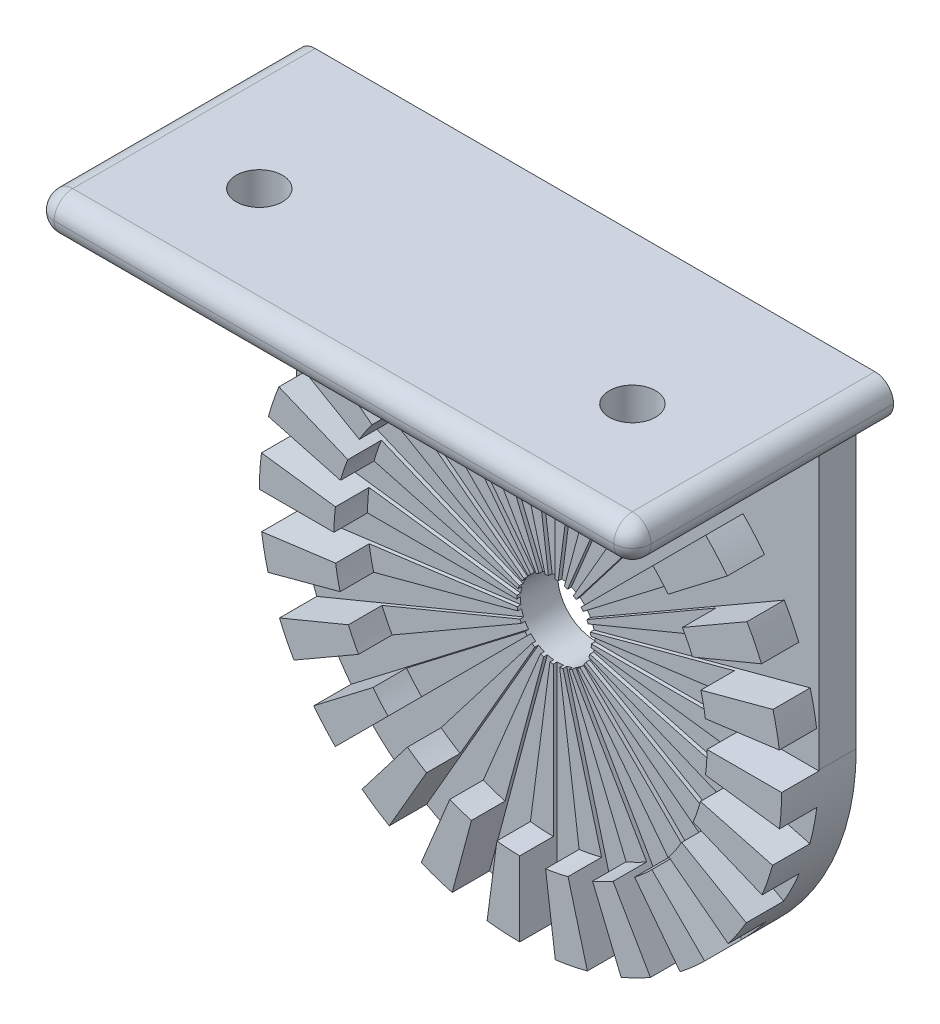
SolidWorks part; units mm, degrees
note: The reader was unsure of these and kept them because the rebuilt part matched: shared geometry of "Sketch1<5>".
ref_plane "Front Plane" through (0, 0, 0) normal (0, 0, 1) x (1, 0, 0)
ref_plane "Top Plane" through (0, 0, 0) normal (0, 1, 0) x (1, 0, 0)
ref_plane "Right Plane" through (0, 0, 0) normal (1, 0, 0) x (0, 0, -1)
sketch "Sketch1" plane through (0, 0, 0) normal (0, 0, 1) x (1, 0, 0)
  line L0 (0, 0) -> (0, 35) construction
  line L1 (0, 0) -> (-35, 0) construction
  line L2 (0, 0) -> (-34.7006, 4.5684) construction
  line L3 (0, 0) -> (-33.8074, 9.0587) construction
  line L4 (0, 0) -> (-32.3358, 13.3939) construction
  line L5 (0, 0) -> (-30.3109, 17.5) construction
  line L6 (0, 0) -> (-27.7674, 21.3067) construction
  line L7 (0, 0) -> (-24.7487, 24.7487) construction
  line L8 (0, 0) -> (-21.3067, 27.7674) construction
  line L9 (0, 0) -> (-17.5, 30.3109) construction
  line L10 (0, 0) -> (-13.3939, 32.3358) construction
  line L11 (0, 0) -> (-9.0587, 33.8074) construction
  line L12 (0, 0) -> (-4.5684, 34.7006) construction
  line L13 (0, 0) -> (0, 35) construction
  line L14 (0, 0) -> (4.5684, 34.7006) construction
  line L15 (0, 0) -> (9.0587, 33.8074) construction
  line L16 (0, 0) -> (13.3939, 32.3358) construction
  line L17 (0, 0) -> (17.5, 30.3109) construction
  line L18 (0, 0) -> (21.3067, 27.7674) construction
  line L19 (0, 0) -> (24.7487, 24.7487) construction
  line L20 (0, 0) -> (27.7674, 21.3067) construction
  line L21 (0, 0) -> (30.3109, 17.5) construction
  line L22 (0, 0) -> (32.3358, 13.3939) construction
  line L23 (0, 0) -> (33.8074, 9.0587) construction
  line L24 (0, 0) -> (34.7006, 4.5684) construction
  line L25 (0, 0) -> (35, 0) construction
  line L26 (0, 0) -> (34.7006, -4.5684) construction
  line L27 (0, 0) -> (33.8074, -9.0587) construction
  line L28 (0, 0) -> (32.3358, -13.3939) construction
  line L29 (0, 0) -> (30.3109, -17.5) construction
  line L30 (0, 0) -> (27.7674, -21.3067) construction
  line L31 (0, 0) -> (24.7487, -24.7487) construction
  line L32 (0, 0) -> (21.3067, -27.7674) construction
  line L33 (0, 0) -> (17.5, -30.3109) construction
  line L34 (0, 0) -> (13.3939, -32.3358) construction
  line L35 (0, 0) -> (9.0587, -33.8074) construction
  line L36 (0, 0) -> (4.5684, -34.7006) construction
  line L37 (0, 0) -> (0, -35) construction
  line L38 (0, 0) -> (-4.5684, -34.7006) construction
  line L39 (0, 0) -> (-9.0587, -33.8074) construction
  line L40 (0, 0) -> (-13.3939, -32.3358) construction
  line L41 (0, 0) -> (-17.5, -30.3109) construction
  line L42 (0, 0) -> (-21.3067, -27.7674) construction
  line L43 (0, 0) -> (-24.7487, -24.7487) construction
  line L44 (0, 0) -> (-27.7674, -21.3067) construction
  line L45 (0, 0) -> (-30.3109, -17.5) construction
  line L46 (0, 0) -> (-32.3358, -13.3939) construction
  line L47 (0, 0) -> (-33.8074, -9.0587) construction
  line L48 (0, 0) -> (-34.7006, -4.5684) construction
  line L49 (0, 0) -> (0, -242.3631) construction
  line L50 (0, 0) -> (261.9224, -229.7808) construction
  line L51 (0, 0) -> (-86.1053, -174.4963) construction
  line L52 (0, 0) -> (-59.0107, -296.2868) construction
  line L53 (0, 0) -> (171.8721, -257.7552) construction
  line L54 (-1.5257, 0.1) -> (-35, 0.1)
  line L55 (-1.5257, 0.1) -> (-34.7136, 4.4693)
  line L56 (-1.4478, 0.4915) -> (-33.7815, 9.1553)
  line L57 (-1.4478, 0.4915) -> (-32.3741, 13.3015)
  line L58 (-1.2713, 0.8495) -> (-30.2609, 17.5866)
  line L59 (-1.2713, 0.8495) -> (-27.8282, 21.2273)
  line L60 (-1.0081, 1.1495) -> (-24.678, 24.8194)
  line L61 (-1.0081, 1.1495) -> (-21.386, 27.7065)
  line L62 (-0.6763, 1.3713) -> (-17.4134, 30.3609)
  line L63 (-0.6763, 1.3713) -> (-13.4863, 32.2975)
  line L64 (-0.2983, 1.4996) -> (-8.9621, 33.8333)
  line L65 (-0.2983, 1.4996) -> (-4.6676, 34.6875)
  line L66 (0.1, 1.5257) -> (0.1, 35)
  line L67 (0.1, 1.5257) -> (4.4693, 34.7136)
  line L68 (0.4915, 1.4478) -> (9.1553, 33.7815)
  line L69 (0.4915, 1.4478) -> (13.3015, 32.3741)
  line L70 (0.8495, 1.2713) -> (17.5866, 30.2609)
  line L71 (0.8495, 1.2713) -> (21.2273, 27.8282)
  line L72 (1.1495, 1.0081) -> (24.8194, 24.678)
  line L73 (1.1495, 1.0081) -> (27.7065, 21.386)
  line L74 (1.3713, 0.6763) -> (30.3609, 17.4134)
  line L75 (1.3713, 0.6763) -> (32.2975, 13.4863)
  line L76 (1.4996, 0.2983) -> (33.8333, 8.9621)
  line L77 (1.4996, 0.2983) -> (34.6875, 4.6676)
  line L78 (1.5257, -0.1) -> (35, -0.1)
  line L79 (1.5257, -0.1) -> (34.7136, -4.4693)
  line L80 (1.4478, -0.4915) -> (33.7815, -9.1553)
  line L81 (1.4478, -0.4915) -> (32.3741, -13.3015)
  line L82 (1.2713, -0.8495) -> (30.2609, -17.5866)
  line L83 (1.2713, -0.8495) -> (27.8282, -21.2273)
  line L84 (1.0081, -1.1495) -> (24.678, -24.8194)
  line L85 (1.0081, -1.1495) -> (21.386, -27.7065)
  line L86 (0.6763, -1.3713) -> (17.4134, -30.3609)
  line L87 (0.6763, -1.3713) -> (13.4863, -32.2975)
  line L88 (0.2983, -1.4996) -> (8.9621, -33.8333)
  line L89 (0.2983, -1.4996) -> (4.6676, -34.6875)
  line L90 (-0.1, -1.5257) -> (-0.1, -35)
  line L91 (-0.1, -1.5257) -> (-4.4693, -34.7136)
  line L92 (-0.4915, -1.4478) -> (-9.1553, -33.7815)
  line L93 (-0.4915, -1.4478) -> (-13.3015, -32.3741)
  line L94 (-0.8495, -1.2713) -> (-17.5866, -30.2609)
  line L95 (-0.8495, -1.2713) -> (-21.2273, -27.8282)
  line L96 (-1.1495, -1.0081) -> (-24.8194, -24.678)
  line L97 (-1.1495, -1.0081) -> (-27.7065, -21.386)
  line L98 (-1.3713, -0.6763) -> (-30.3609, -17.4134)
  line L99 (-1.3713, -0.6763) -> (-32.2975, -13.4863)
  line L100 (-1.4996, -0.2983) -> (-33.8333, -8.9621)
  line L101 (-1.4996, -0.2983) -> (-34.6875, -4.6676)
  line L102 (0, 0) -> (-192.6466, -219.5626) construction
  line L103 (0, 0) -> (183.0194, 0) construction
  circle A0 centre (0, 0) radius 35
  arc A1 (-34.7136, 4.4693) -> (-35, 0.1) centre (-1.5257, 0.1) ccw
  arc A2 (-32.3741, 13.3015) -> (-33.7815, 9.1553) centre (-1.4478, 0.4915) ccw
  arc A3 (-27.8282, 21.2273) -> (-30.2609, 17.5866) centre (-1.2713, 0.8495) ccw
  arc A4 (-21.386, 27.7065) -> (-24.678, 24.8194) centre (-1.0081, 1.1495) ccw
  arc A5 (-13.4863, 32.2975) -> (-17.4134, 30.3609) centre (-0.6763, 1.3713) ccw
  arc A6 (-4.6676, 34.6875) -> (-8.9621, 33.8333) centre (-0.2983, 1.4996) ccw
  arc A7 (4.4693, 34.7136) -> (0.1, 35) centre (0.1, 1.5257) ccw
  arc A8 (13.3015, 32.3741) -> (9.1553, 33.7815) centre (0.4915, 1.4478) ccw
  arc A9 (21.2273, 27.8282) -> (17.5866, 30.2609) centre (0.8495, 1.2713) ccw
  arc A10 (27.7065, 21.386) -> (24.8194, 24.678) centre (1.1495, 1.0081) ccw
  arc A11 (32.2975, 13.4863) -> (30.3609, 17.4134) centre (1.3713, 0.6763) ccw
  arc A12 (34.6875, 4.6676) -> (33.8333, 8.9621) centre (1.4996, 0.2983) ccw
  arc A13 (34.7136, -4.4693) -> (35, -0.1) centre (1.5257, -0.1) ccw
  arc A14 (32.3741, -13.3015) -> (33.7815, -9.1553) centre (1.4478, -0.4915) ccw
  arc A15 (27.8282, -21.2273) -> (30.2609, -17.5866) centre (1.2713, -0.8495) ccw
  arc A16 (21.386, -27.7065) -> (24.678, -24.8194) centre (1.0081, -1.1495) ccw
  arc A17 (13.4863, -32.2975) -> (17.4134, -30.3609) centre (0.6763, -1.3713) ccw
  arc A18 (4.6676, -34.6875) -> (8.9621, -33.8333) centre (0.2983, -1.4996) ccw
  arc A19 (-4.4693, -34.7136) -> (-0.1, -35) centre (-0.1, -1.5257) ccw
  arc A20 (-13.3015, -32.3741) -> (-9.1553, -33.7815) centre (-0.4915, -1.4478) ccw
  arc A21 (-21.2273, -27.8282) -> (-17.5866, -30.2609) centre (-0.8495, -1.2713) ccw
  arc A22 (-27.7065, -21.386) -> (-24.8194, -24.678) centre (-1.1495, -1.0081) ccw
  arc A23 (-32.2975, -13.4863) -> (-30.3609, -17.4134) centre (-1.3713, -0.6763) ccw
  arc A24 (-34.6875, -4.6676) -> (-33.8333, -8.9621) centre (-1.4996, -0.2983) ccw
  point P25 (0, 0)
  point P31 (0, 0)
  point P57 (0, 0)
  point P58 (0, 0)
  point P159 (0, 0)
  dimension "D1" = 70
  dimension "D8" = 24
  dimension "D2" = 11.264
  dimension "D3" = 48.74
  dimension "D4" = 26.264
  dimension "D5" = 33.696
  dimension "D9" = 41.264
  dimension "D7" = 0.1
  dimension "D6" = 48
extrude "Boss-Extrude2" add sketch "Sketch1" along normal blind 10 contours L55 A0 L54 | L57 A0 L56 | L59 A0 L58 | L61 A0 L60 | L63 A0 L62 | L65 A0 L64 | L67 A0 L66 | L69 A0 L68 | L71 A0 L70 | L73 A0 L72 | L75 A0 L74 | L77 A0 L76 | L79 A0 L78 | L81 A0 L80 | L83 A0 L82 | L85 A0 L84 | L87 A0 L86 | L89 A0 L88 | L91 A0 L90 | L93 A0 L92 | L95 A0 L94 | L97 A0 L96 | L101 A0 L100 | L99 A0 L98
extrude "Boss-Extrude3" add sketch "Sketch1<5>" along normal blind 5 contours L3 A0 L2 | L5 A0 L4 | L7 A0 L6 | L9 A0 L8 | L11 A0 L10 | L13 A0 L12 | L15 A0 L14 | L17 A0 L16 | L19 A0 L18 | L21 A0 L20 | L23 A0 L22 | L25 A0 L24 | L27 A0 L26 | L29 A0 L28 | L31 A0 L30 | L33 A0 L32 | L35 A0 L34 | L37 A0 L36 | L39 A0 L38 | L41 A0 L40 | L43 A0 L42 | L45 A0 L44 | L47 A0 L46 | L1 A0 L48
sketch "Sketch1<5>" plane through (0, 0, 0) normal (0, 0, 1) x (1, 0, 0) same geometry as "Sketch1"
sketch "Sketch3" plane through (0, 0, 0) normal (0, 0, 1) x (1, 0, 0)
  circle A0 centre (0, 0) radius 5
  dimension "D1" = 10
extrude "Cut-Extrude1" cut sketch "Sketch3" against normal through all and the other way through all
sketch "Sketch9" plane through (0, 0, 0) normal (0, 0, 1) x (1, 0, 0)
  circle A0 centre (0, 0) radius 25
  dimension "D1" = 50
extrude "Cut-Extrude6" cut sketch "Sketch9" along normal blind 5.5 from offset 5.5
ref_plane "Plane1" through (0, 40, 0) normal (0, 1, 0) x (1, 0, 0)
sketch "Sketch4" plane through (0, 40, 0) normal (0, 1, 0) x (1, 0, 0)
  line L0 (-68.9774, 0) -> (62.7068, 0) construction
  line L1 (40, -35) -> (-40, -35)
  line L2 (40, -35) -> (40, 0)
  line L4 (-40, -35) -> (-40, 0)
  line L5 (40, -35) -> (-40, 35) construction
  line L6 (40, 35) -> (-40, -35) construction
  line L7 (-40, 0) -> (40, 0)
  point P0 (0, 0)
  dimension "D1" = 80
  dimension "D2" = 35
  dimension "D3" = 40
extrude "Boss-Extrude4" add sketch "Sketch4" along normal blind 5 contours L2 L7 L4 L1
sketch "Sketch6" plane through (0, 45, 0) normal (0, 1, 0) x (1, 0, 0)
  line L0 (-40, -35) -> (-40, 0) construction
  line L2 (0, 0) -> (19.5699, 0) construction
  line L3 (0, 0) -> (0, 22.0266) construction
  line L4 (40, -35) -> (-40, -35) construction
  circle A1 centre (-25, -20) radius 3.1
  circle A2 centre (25, -20) radius 3.1
  dimension "D3" = 6.2
  dimension "D1" = 15
  dimension "D2" = 15
extrude "Cut-Extrude2" cut sketch "Sketch6" against normal through all
sketch "Sketch10" plane through (0, 0, 0) normal (0, 0, 1) x (1, 0, 0)
  line L0 (-35, 0) -> (-35, 40)
  line L2 (38.5, 40) -> (-38.5, 40) construction
  line L3 (35, 0) -> (35, 40)
  line L4 (-35, 40) -> (35, 40)
  arc A0 (-34.9999, 0.1) -> (-34.6874, -4.6675) centre (0, 0) ccw construction
  arc A3 (-35, 0) -> (35, 0) centre (0, 0) cw
extrude "Boss-Extrude5" add sketch "Sketch10" along normal blind 5
fillet "Fillet2" radius 2.5 15 edges at (40, 45, 17.5) (37.5, 40, 0) (35, 40, 2.5) (-35, 40, 2.5) (0, 40, 5) (0, 45, 35) (40, 40, 17.5) (-37.5, 40, 0) (-40, 40, 17.5) (0, 40, 35) (40, 42.5, 35) (40, 42.5, 0) (-40, 42.5, 0) (-40, 42.5, 35) (-40, 45, 17.5)
